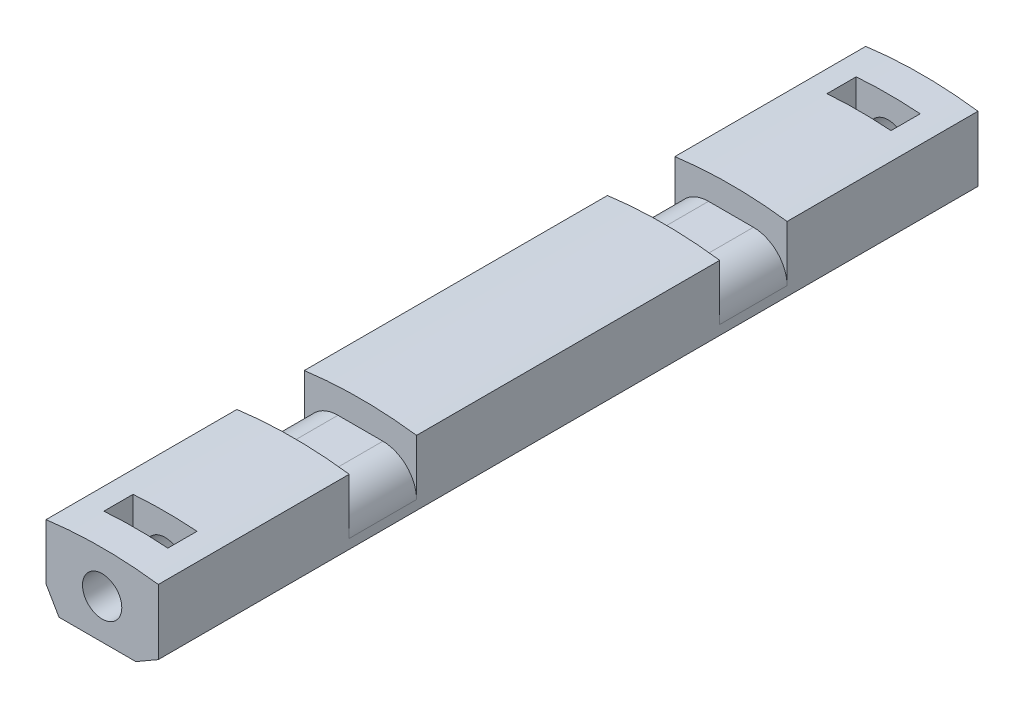
SolidWorks part; units mm, degrees
ref_plane "Plan de face" through (0, 0, 0) normal (0, 0, 1) x (1, 0, 0)
ref_plane "Plan de dessus" through (0, 0, 0) normal (0, 1, 0) x (1, 0, 0)
ref_plane "Plan de droite" through (0, 0, 0) normal (1, 0, 0) x (0, 0, -1)
sketch "Esquisse3" plane through (0, 0, 0) normal (0, 0, 1) x (1, 0, 0)
  line L0 (-5, 30.2141) -> (-5, 37.1652)
  line L1 (5, 30.2141) -> (5, 37.1652)
  line L2 (-5, 30.2141) -> (5, 30.2141)
  line L3 (-5, 37.1652) -> (5, 37.1652) construction
  line L4 (-5, 37.1652) -> (-5, 0) construction
  line L5 (-5, 0) -> (5, 0) construction
  line L6 (5, 37.1652) -> (5, 0) construction
  line L7 (8.9994, 41.4168) -> (9.1038, 41.3823)
  circle A0 centre (0, 0) radius 37.5 construction
  circle A1 centre (0, 0) radius 30.625 construction
  arc A2 (-5, 37.1652) -> (5, 37.1652) centre (0, 0) cw
  point P5 (0, 0)
  dimension "D1" = 75
  dimension "D2" = 61.25
  dimension "D3" = 10
extrude "Boss.-Extru.2" add sketch "Esquisse3" along normal blind 73 contours A2 L0 L2 L1
sketch "Esquisse6" plane through (-5, 0, 0) normal (-1, 0, 0) x (0, 0, 1)
  line L0 (73, 30.2141) -> (0, 30.2141) construction
  line L1 (17, 35.2141) -> (23, 35.2141)
  line L2 (17, 35.2141) -> (17, 40.2141)
  line L3 (17, 40.2141) -> (23, 40.2141)
  line L4 (23, 35.2141) -> (23, 40.2141)
  line L5 (50, 35.2141) -> (56, 35.2141)
  line L6 (50, 35.2141) -> (50, 40.2141)
  line L7 (50, 40.2141) -> (56, 40.2141)
  line L8 (56, 35.2141) -> (56, 40.2141)
  line L9 (17, 35.2141) -> (0, 35.2141) construction
  line L10 (0, 30.2141) -> (0, 37.1652) construction
  line L11 (56, 35.2141) -> (73, 35.2141) construction
  line L12 (73, 30.2141) -> (73, 37.1652) construction
  dimension "D1" = 5
  dimension "D2" = 6
  dimension "D3" = 5
  dimension "D4" = 17
extrude "Enlèv. mat.-Extru.3" cut sketch "Esquisse6" against normal through all
sketch "Esquisse7" plane through (0, 0, 73) normal (0, 0, 1) x (1, 0, 0)
  line L0 (-30, 0) -> (-37.5, 0) construction
  circle A0 centre (0, 0) radius 33.75 construction
  circle A1 centre (0, 33.75) radius 1.75
  circle A2 centre (0, 0) radius 37.5 construction
  circle A3 centre (0, 0) radius 30 construction
  arc A4 (5, 37.1652) -> (-5, 37.1652) centre (0, 0) ccw construction
  point P12 (-33.75, 0)
  dimension "D2" = 3.5
  dimension "D3" = 60
extrude "Enlèv. mat.-Extru.4" cut sketch "Esquisse7" against normal blind 12
sketch "Esquisse8" plane through (0, 0, 0) normal (0, 0, -1) x (-1, 0, 0)
  line L0 (-30, 0) -> (-37.5, 0) construction
  circle A0 centre (0, 0) radius 33.75 construction
  circle A1 centre (0, 33.75) radius 1.75
  circle A2 centre (0, 0) radius 37.5 construction
  circle A3 centre (0, 0) radius 30 construction
  arc A4 (5, 37.1652) -> (-5, 37.1652) centre (0, 0) ccw construction
  point P9 (-33.75, 0)
  dimension "D2" = 3.5
  dimension "D3" = 60
extrude "Enlèv. mat.-Extru.5" cut sketch "Esquisse8" against normal blind 12
fillet "Congé1" radius 3 4 edges at (5, 35.2141, 53) (-5, 35.2141, 53) (5, 35.2141, 20) (-5, 35.2141, 20)
sketch "Esquisse9" plane through (0, 0, 0) normal (0, 0, -1) x (-1, 0, 0)
  line L0 (-2.85, 37.3915) -> (-2.85, 31.9954)
  line L1 (-2.85, 31.9954) -> (0, 30.35)
  line L2 (0, 30.35) -> (2.85, 31.9954)
  line L3 (2.85, 31.9954) -> (2.85, 37.3915)
  line L4 (-2.85, 31.9954) -> (2.85, 31.9954) construction
  arc A0 (5, 37.1652) -> (-5, 37.1652) centre (0, 0) ccw construction
  arc A1 (2.85, 37.3915) -> (-2.85, 37.3915) centre (0, 0) ccw
  circle A2 centre (0, 33.75) radius 1.75 construction
  point P9 (0, 31.9954)
  dimension "D3" = 3.4
  dimension "D1" = 120
  dimension "D2" = 5.7
extrude "Enlèv. mat.-Extru.6" cut sketch "Esquisse9" against normal blind 2.6 from offset 3 offset against normal yes
sketch "Esquisse10" plane through (0, 0, 73) normal (0, 0, 1) x (1, 0, 0)
  line L0 (-2.85, 37.3915) -> (-2.85, 31.9954)
  line L1 (-2.85, 31.9954) -> (0, 30.35)
  line L2 (0, 30.35) -> (2.85, 31.9954)
  line L3 (2.85, 31.9954) -> (2.85, 37.3915)
  line L4 (-2.85, 31.9954) -> (2.85, 31.9954) construction
  line L5 (-1.75, 33.75) -> (1.75, 33.75) construction
  line L6 (0, 35.5) -> (0, 32) construction
  circle A0 centre (0, 33.75) radius 1.75 construction
  arc A1 (2.85, 37.3915) -> (-2.85, 37.3915) centre (0, 0) ccw
  circle A2 centre (0, 33.75) radius 1.75 construction
  arc A3 (5, 37.1652) -> (-5, 37.1652) centre (0, 0) ccw construction
  point P9 (0, 31.9954)
  point P19 (0, 33.75)
  dimension "D3" = 3.4
  dimension "D1" = 120
  dimension "D2" = 5.7
extrude "Enlèv. mat.-Extru.7" cut sketch "Esquisse10" against normal blind 2.6 from offset 3 offset against normal yes
chamfer "Chanfrein1" distance 2 angle 30 2 edges at (5, 30.2141, 36.5) (-5, 30.2141, 36.5)
